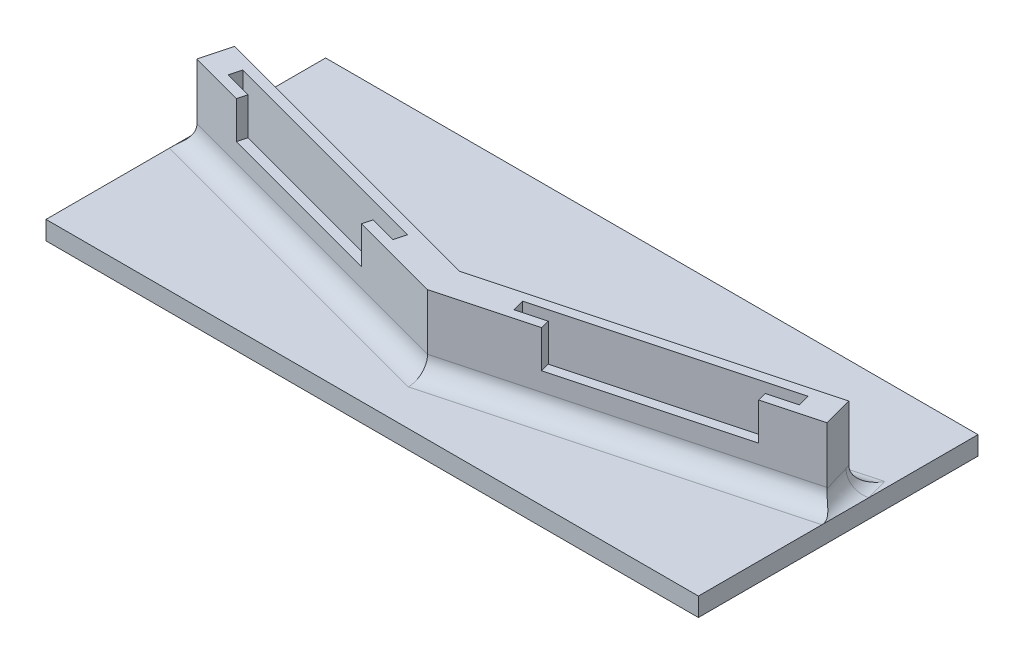
SolidWorks part; units mm, degrees
note: The reader was unsure of these and kept them because the rebuilt part matched: shared geometry of "스케치1<3>", "스케치1<5>".
ref_plane "정면" through (0, 0, 0) normal (0, 0, 1) x (1, 0, 0)
ref_plane "윗면" through (0, 0, 0) normal (0, 1, 0) x (1, 0, 0)
ref_plane "우측면" through (0, 0, 0) normal (1, 0, 0) x (0, 0, -1)
sketch "스케치1" plane through (0, 0, 0) normal (0, 1, 0) x (1, 0, 0)
  line L0 (-53.6129, 0) -> (53.6129, 0) construction
  line L1 (0, 0) -> (-33.8074, 9.0587)
  line L2 (0, 0) -> (33.8074, 9.0587)
  line L3 (0, 1.0353) -> (33.5486, 10.0246)
  line L4 (0, 1.0353) -> (-33.5486, 10.0246)
  line L5 (0, 2.3811) -> (33.2121, 11.2803)
  line L6 (0, 2.3811) -> (-33.2121, 11.2803)
  line L9 (0, 3.4164) -> (32.9533, 12.2462)
  line L10 (0, 3.4164) -> (-32.9533, 12.2462)
  line L11 (-33.8074, 9.0587) -> (-32.9533, 12.2462)
  line L12 (33.8074, 9.0587) -> (32.9533, 12.2462)
  line L13 (-6.7615, 1.8117) -> (-5.9074, 4.9993)
  line L14 (6.7615, 1.8117) -> (5.9074, 4.9993)
  line L15 (-30.9096, 8.2822) -> (-30.0555, 11.4698)
  line L16 (30.9096, 8.2822) -> (30.0555, 11.4698)
  line L17 (28.0118, 7.5058) -> (27.753, 8.4717)
  line L18 (-28.0118, 7.5058) -> (-27.753, 8.4717)
  line L19 (9.4004, 3.5541) -> (9.6593, 2.5882)
  line L20 (-9.4004, 3.5541) -> (-9.6593, 2.5882)
  point P3 (0, 0)
  dimension "D1" = 15
  dimension "D2" = 15
  dimension "D3" = 35
  dimension "D4" = 35
  dimension "D8" = 3
  dimension "D9" = 3
  dimension "D10" = 25
  dimension "D11" = 25
  dimension "D12" = 3
  dimension "D13" = 3
  dimension "D14" = 3
  dimension "D15" = 3
  dimension "D5" = 1
  dimension "D6" = 1.3
  dimension "D7" = 1
extrude "보스-돌출1" add sketch "스케치1" along normal blind 4 contours L1 L13 L4 L11 | L2 L14 L3 L4 L13 L1 | L14 L2 L12 L3 | L3 L14 L5 L6 L13 L4 | L5 L14 L9 L10 L13 L6 | L6 L13 L10 L11 | L14 L5 L12 L9 | L1 L15 L4 L11 | L4 L15 L6 L11 | L6 L15 L10 L11 | L16 L5 L12 L9 | L16 L3 L12 L5 | L16 L2 L12 L3 | L17 L2 L16 L3 | L1 L18 L4 L15 | L4 L20 L1 L13 | L19 L3 L14 L2
extrude "보스-돌출2" add sketch "스케치1<3>" along normal blind 1.5 contours L3 L16 L5 L14 | L15 L4 L13 L6
sketch "스케치1<3>" plane through (0, 0, 0) normal (0, 1, 0) x (1, 0, 0) same geometry as "스케치1"
sketch "스케치2" plane through (0, 0, 0) normal (0, -1, 0) x (1, 0, 0)
  line L0 (0, 5.9413) -> (0, -24.0587) construction
  line L1 (-35, 5.9413) -> (35, 5.9413)
  line L2 (-35, 5.9413) -> (-35, -24.0587)
  line L3 (-35, -24.0587) -> (35, -24.0587)
  line L4 (35, 5.9413) -> (35, -24.0587)
  line L5 (0, 0) -> (0, -3.4164) construction
  line L6 (0, -3.4164) -> (-32.9533, -12.2462) construction
  line L7 (-33.8074, -9.0587) -> (33.8074, -9.0587) construction
  line L8 (-35, -9.0587) -> (35, -9.0587) construction
  dimension "D1" = 70
  dimension "D2" = 30
extrude "보스-돌출3" add sketch "스케치2" along normal blind 2
extrude "보스-돌출4" add sketch "스케치1<5>" along normal blind 8 contours L5 L16 L9 L14 | L16 L5 L12 L9 | L16 L3 L12 L5 | L16 L2 L12 L3 | L17 L2 L16 L3 | L15 L6 L13 L10 | L6 L15 L10 L11 | L4 L15 L6 L11 | L1 L15 L4 L11 | L1 L18 L4 L15 | L5 L14 L9 L10 L13 L6 | L3 L14 L5 L6 L13 L4 | L2 L14 L3 L4 L13 L1 | L4 L20 L1 L13 | L19 L3 L14 L2
sketch "스케치1<5>" plane through (0, 0, 0) normal (0, 1, 0) x (1, 0, 0) same geometry as "스케치1"
fillet "필렛1" radius 2 6 edges at (-33.3804, 0, -10.6524) (-16.4767, 0, -7.8313) (16.4767, 0, -7.8313) (33.3804, 0, -10.6524) (-16.9037, 0, -4.5293) (16.9037, 0, -4.5293)
